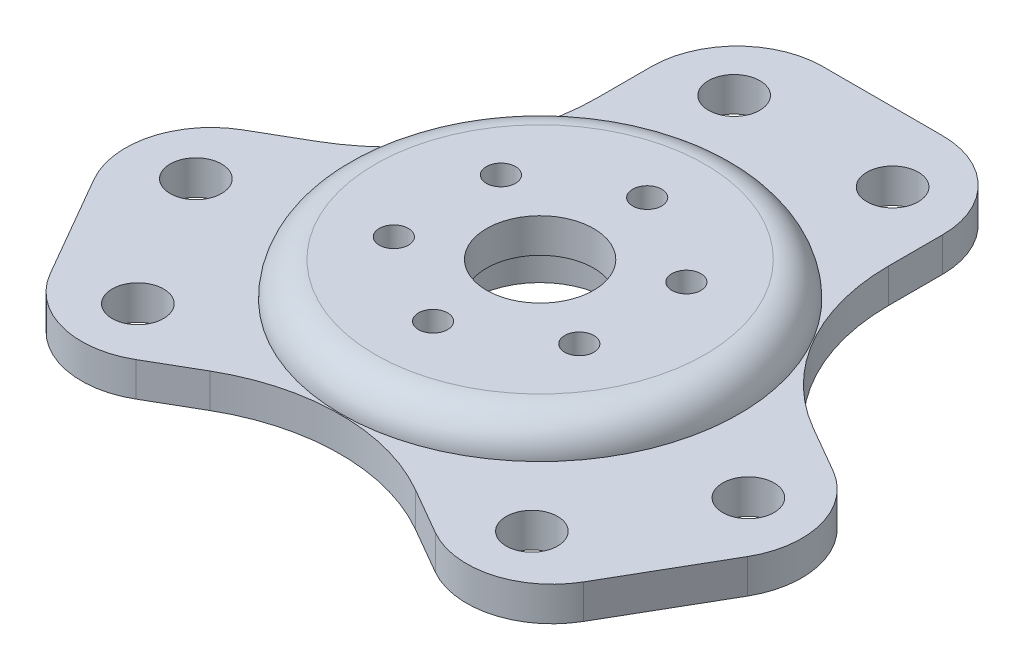
SolidWorks part; units mm, degrees
ref_plane "Front" through (0, 0, 0) normal (0, 0, 1) x (1, 0, 0)
ref_plane "Top" through (0, 0, 0) normal (0, 1, 0) x (1, 0, 0)
ref_plane "Right" through (0, 0, 0) normal (1, 0, 0) x (0, 0, -1)
sketch "Эскиз1" plane through (0, 0, 0) normal (0, 1, 0) x (1, 0, 0)
  line L0 (-17, 9.815) -> (-17, 40)
  line L1 (-17, 40) -> (17, 40)
  line L2 (17, 40) -> (17, 9.815)
  line L3 (17, 9.815) -> (43.141, -5.2776)
  line L4 (43.141, -5.2776) -> (26.141, -34.7224)
  line L5 (26.141, -34.7224) -> (0, -19.6299)
  line L6 (0, -19.6299) -> (-26.141, -34.7224)
  line L7 (-26.141, -34.7224) -> (-43.141, -5.2776)
  line L8 (-43.141, -5.2776) -> (-17, 9.815)
  line L9 (0, 0) -> (0, 40) construction
  line L10 (0, 0) -> (34.641, -20) construction
  line L11 (0, 0) -> (-34.641, -20) construction
  circle A0 centre (0, 0) radius 6.25
  point P12 (0, 40)
  dimension "D3" = 12.5
  dimension "D1" = 34
  dimension "D2" = 40
extrude "База" add sketch "Эскиз1" along normal blind 8
sketch "Эскиз2" plane through (0, 0, 0) normal (0, 1, 0) x (1, 0, 0)
  circle A0 centre (0, 0) radius 8
  dimension "D1" = 16
extrude "ВырезЦентр" cut sketch "Эскиз2" along normal blind 4
sketch "Эскиз3" plane through (0, 8, 0) normal (0, 1, 0) x (1, 0, 0)
  circle A0 centre (0, 12.5) radius 1.7
  dimension "D1" = 3.4
  dimension "D2" = 12.5
extrude "Вырез-3" cut sketch "Эскиз3" against normal through all
pattern_circular "Круговой массив1" count 6 over 360 about axis through (0, 4, 0) along (0, 1, 0) of "Вырез-3"
sketch "Эскиз4" plane through (0, 8, 0) normal (0, -1, 0) x (1, 0, 0)
  circle A0 centre (0, 0) radius 47.5
  circle A1 centre (0, 0) radius 23.25
  dimension "D1" = 95
  dimension "D2" = 46.5
extrude "Вырез-Вытянуть3" cut sketch "Эскиз4" along normal blind 4
fillet "Скругление1" radius 10 6 edges at (-17, 2, -40) (17, 2, -40) (43.141, 2, 5.2776) (26.141, 2, 34.7224) (-43.141, 2, 5.2776) (-26.141, 2, 34.7224)
fillet "Скругление2" radius 24 3 edges at (17, 4, -9.815) (-17, 4, -9.815) (0, 4, 19.6299)
fillet "Скругление3" radius 4 1 edges at (0, 8, -23.25)
sketch "Эскиз5" plane through (0, 4, 0) normal (0, 1, 0) x (-1, 0, 0)
  line L0 (-34.641, 20) -> (0, 0) construction
  line L1 (-38.141, 13.9378) -> (-31.141, 26.0622) construction
  line L2 (0, 0) -> (0, -40) construction
  line L3 (7, -40) -> (-7, -40) construction
  circle A1 centre (-9.25, -31.8984) radius 3
  circle A3 centre (-32.2498, 7.9385) radius 3
  circle A4 centre (0, 0) radius 33.2125 construction
  dimension "D1" = 6
  dimension "D4" = 9.25
  dimension "D2" = 66.425
  dimension "D3" = 9.25
extrude "ВырезМагнита" cut sketch "Эскиз5" against normal through all
pattern_circular "Круговой массив2" count 3 over 360 about axis through (0, 4, 0) along (0, -1, 0) of "ВырезМагнита"
